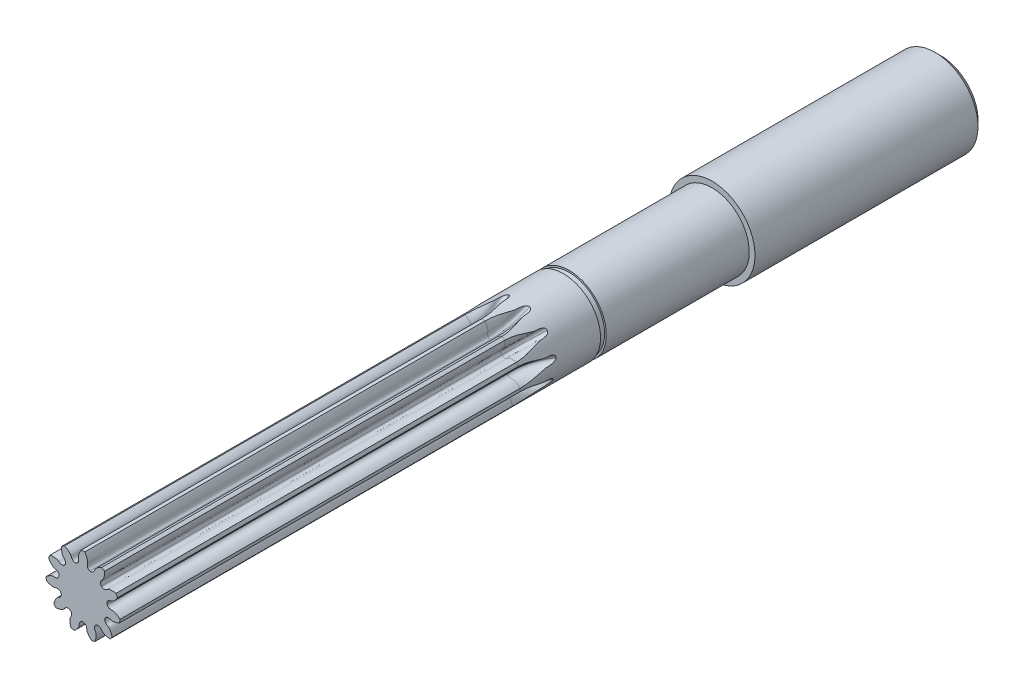
SolidWorks part; units mm, degrees
ref_plane "Спереди" through (0, 0, 0) normal (0, 0, 1) x (1, 0, 0)
ref_plane "Сверху" through (0, 0, 0) normal (0, 1, 0) x (1, 0, 0)
ref_plane "Справа" through (0, 0, 0) normal (1, 0, 0) x (0, 0, -1)
other "Configuration Table"
sketch "Эскиз1" plane through (0, 0, 0) normal (0, 0, 1) x (1, 0, 0)
  line L0 (0, 4.2505) -> (0, 6.5001) construction
  arc A6 (0.303, 6.493) -> (-0.303, 6.493) centre (0, 0) ccw
  arc A8 (3.7653, 5.2984) -> (3.2555, 5.6261) centre (0, 0) ccw
  arc A9 (6.0321, 2.4217) -> (5.7804, 2.9729) centre (0, 0) ccw
  arc A10 (6.3838, -1.224) -> (6.47, -0.6241) centre (0, 0) ccw
  arc A11 (4.7087, -4.481) -> (5.1055, -4.023) centre (0, 0) ccw
  arc A12 (1.5386, -6.3154) -> (2.12, -6.1446) centre (0, 0) ccw
  arc A13 (-2.12, -6.1446) -> (-1.5386, -6.3154) centre (0, 0) ccw
  arc A14 (-5.1055, -4.023) -> (-4.7087, -4.481) centre (0, 0) ccw
  arc A15 (-6.47, -0.6241) -> (-6.3838, -1.224) centre (0, 0) ccw
  arc A16 (-5.7804, 2.9729) -> (-6.0321, 2.4217) centre (0, 0) ccw
  arc A17 (-3.2555, 5.6261) -> (-3.7653, 5.2984) centre (0, 0) ccw
  arc A18 (-4.1999, 0.6538) -> (-4.214, 0.5559) centre (0, 0) ccw
  arc A19 (-3.1797, 2.8207) -> (-3.2445, 2.746) centre (0, 0) ccw
  arc A20 (-1.15, 4.092) -> (-1.2449, 4.0641) centre (0, 0) ccw
  arc A21 (1.2449, 4.0641) -> (1.15, 4.092) centre (0, 0) ccw
  arc A22 (3.2445, 2.746) -> (3.1797, 2.8207) centre (0, 0) ccw
  arc A23 (4.214, 0.5559) -> (4.1999, 0.6538) centre (0, 0) ccw
  arc A24 (3.8456, -1.8106) -> (3.8867, -1.7206) centre (0, 0) ccw
  arc A25 (2.2563, -3.6023) -> (2.3394, -3.5488) centre (0, 0) ccw
  arc A26 (-0.0494, -4.2502) -> (0.0494, -4.2502) centre (0, 0) ccw
  arc A27 (-2.3394, -3.5488) -> (-2.2563, -3.6023) centre (0, 0) ccw
  arc A28 (-3.8867, -1.7206) -> (-3.8456, -1.8106) centre (0, 0) ccw
  spline S0 degree 3 poles (0.303, 6.493) (0.3466, 6.4296) (0.4149, 6.3229) (0.5038, 6.1711) (0.5716, 6.0406) (0.6313, 5.9095) (0.6852, 5.7791) (0.7296, 5.6484) (0.7674, 5.5183) (0.798, 5.3728) (0.8278, 5.1961) (0.7682, 4.9723) (0.7367, 4.7556) (0.754, 4.5684) (0.7852, 4.4471) (0.829, 4.3517) (0.8776, 4.2755) (0.9328, 4.2146) (1.0177, 4.1438) (1.0937, 4.1064) (1.15, 4.092) knots 0 0 0 0 0.085617 0.14097 0.195721 0.24917 0.301247 0.352629 0.402768 0.451734 0.518548 0.599046 0.705842 0.760988 0.807057 0.844573 0.877292 0.907236 0.935686 1 1 1 1
  spline S1 degree 3 poles (-0.303, 6.493) (-0.3466, 6.4296) (-0.4149, 6.3229) (-0.5038, 6.1711) (-0.5716, 6.0406) (-0.6313, 5.9095) (-0.6852, 5.7791) (-0.7296, 5.6484) (-0.7674, 5.5183) (-0.798, 5.3728) (-0.8278, 5.1961) (-0.7682, 4.9723) (-0.7367, 4.7556) (-0.754, 4.5684) (-0.7852, 4.4471) (-0.829, 4.3517) (-0.8776, 4.2755) (-0.9328, 4.2146) (-1.0177, 4.1438) (-1.0937, 4.1064) (-1.15, 4.092) knots 0 0 0 0 0.085617 0.14097 0.195721 0.24917 0.301247 0.352629 0.402768 0.451734 0.518548 0.599046 0.705842 0.760988 0.807057 0.844573 0.877292 0.907236 0.935686 1 1 1 1
  spline S2 degree 3 poles (3.2555, 5.6261) (3.1845, 5.5963) (3.0694, 5.5435) (2.9125, 5.4638) (2.7849, 5.3907) (2.6639, 5.3126) (2.548, 5.2321) (2.4399, 5.1462) (2.3379, 5.0572) (2.2335, 4.9513) (2.1128, 4.8187) (2.042, 4.5983) (1.9513, 4.399) (1.8356, 4.2508) (1.7437, 4.1657) (1.6553, 4.1091) (1.5733, 4.0713) (1.4939, 4.0498) (1.3841, 4.0362) (1.3, 4.0458) (1.2449, 4.0641) knots 0 0 0 0 0.085617 0.14097 0.195721 0.24917 0.301247 0.352629 0.402768 0.451734 0.518548 0.599046 0.705842 0.760988 0.807057 0.844573 0.877292 0.907236 0.935686 1 1 1 1
  spline S3 degree 3 poles (3.7653, 5.2984) (3.7677, 5.2215) (3.7674, 5.0948) (3.7602, 4.9191) (3.7467, 4.7726) (3.7259, 4.6301) (3.7008, 4.4913) (3.6676, 4.3573) (3.629, 4.2274) (3.5761, 4.0885) (3.5056, 3.9237) (3.3345, 3.7676) (3.1908, 3.6024) (3.1041, 3.4356) (3.0649, 3.3166) (3.0502, 3.2127) (3.0498, 3.1224) (3.0633, 3.0412) (3.0965, 2.9357) (3.1402, 2.8632) (3.1797, 2.8207) knots 0 0 0 0 0.085617 0.14097 0.195721 0.24917 0.301247 0.352629 0.402768 0.451734 0.518548 0.599046 0.705842 0.760988 0.807057 0.844573 0.877292 0.907236 0.935686 1 1 1 1
  spline S4 degree 3 poles (5.7804, 2.9729) (5.7046, 2.9862) (5.5791, 3.004) (5.4041, 3.0219) (5.2573, 3.0293) (5.1132, 3.0291) (4.9722, 3.024) (4.8349, 3.0101) (4.7009, 2.9904) (4.5558, 2.9578) (4.3826, 2.9115) (4.2038, 2.7644) (4.0198, 2.6457) (3.8424, 2.5836) (3.719, 2.5617) (3.6141, 2.5619) (3.5246, 2.5744) (3.4462, 2.5993) (3.3465, 2.6472) (3.281, 2.7007) (3.2445, 2.746) knots 0 0 0 0 0.085617 0.14097 0.195721 0.24917 0.301247 0.352629 0.402768 0.451734 0.518548 0.599046 0.705842 0.760988 0.807057 0.844573 0.877292 0.907236 0.935686 1 1 1 1
  spline S5 degree 3 poles (6.0321, 2.4217) (5.9925, 2.3557) (5.9238, 2.2492) (5.8227, 2.1053) (5.7322, 1.9894) (5.6377, 1.8807) (5.5415, 1.7775) (5.4411, 1.6827) (5.3384, 1.5943) (5.2188, 1.5061) (5.0704, 1.4055) (4.8421, 1.3668) (4.6319, 1.3054) (4.4688, 1.212) (4.3714, 1.1331) (4.3029, 1.0537) (4.2537, 0.9778) (4.2212, 0.9023) (4.1921, 0.7956) (4.1897, 0.711) (4.1999, 0.6538) knots 0 0 0 0 0.085617 0.14097 0.195721 0.24917 0.301247 0.352629 0.402768 0.451734 0.518548 0.599046 0.705842 0.760988 0.807057 0.844573 0.877292 0.907236 0.935686 1 1 1 1
  spline S6 degree 3 poles (6.47, -0.6241) (6.4135, -0.572) (6.3176, -0.4892) (6.18, -0.3795) (6.0605, -0.2938) (5.9391, -0.2162) (5.8178, -0.1442) (5.6948, -0.0816) (5.5714, -0.0258) (5.4317, 0.0252) (5.261, 0.0799) (5.031, 0.0528) (4.812, 0.0524) (4.6292, 0.0961) (4.5136, 0.1444) (4.4254, 0.2013) (4.3569, 0.2602) (4.3044, 0.3235) (4.2465, 0.4177) (4.2203, 0.4982) (4.214, 0.5559) knots 0 0 0 0 0.085617 0.14097 0.195721 0.24917 0.301247 0.352629 0.402768 0.451734 0.518548 0.599046 0.705842 0.760988 0.807057 0.844573 0.877292 0.907236 0.935686 1 1 1 1
  spline S7 degree 3 poles (6.3838, -1.224) (6.3148, -1.2581) (6.1995, -1.3105) (6.0366, -1.3769) (5.8978, -1.4255) (5.7595, -1.4658) (5.6228, -1.5007) (5.4871, -1.5261) (5.3529, -1.5449) (5.2046, -1.5545) (5.0254, -1.5588) (4.8124, -1.468) (4.6023, -1.406) (4.4146, -1.3964) (4.2901, -1.4101) (4.1895, -1.4399) (4.1071, -1.4771) (4.0389, -1.5231) (3.9568, -1.5971) (3.909, -1.667) (3.8867, -1.7206) knots 0 0 0 0 0.085617 0.14097 0.195721 0.24917 0.301247 0.352629 0.402768 0.451734 0.518548 0.599046 0.705842 0.760988 0.807057 0.844573 0.877292 0.907236 0.935686 1 1 1 1
  spline S8 degree 3 poles (5.1055, -4.023) (5.0861, -3.9486) (5.0502, -3.827) (4.9937, -3.6604) (4.9395, -3.5237) (4.8795, -3.3928) (4.8163, -3.2667) (4.7466, -3.1475) (4.673, -3.0338) (4.5831, -2.9154) (4.469, -2.7771) (4.2609, -2.6756) (4.0765, -2.5575) (3.9463, -2.4219) (3.8751, -2.3188) (3.8317, -2.2233) (3.8059, -2.1366) (3.796, -2.055) (3.7981, -1.9445) (3.8196, -1.8626) (3.8456, -1.8106) knots 0 0 0 0 0.085617 0.14097 0.195721 0.24917 0.301247 0.352629 0.402768 0.451734 0.518548 0.599046 0.705842 0.760988 0.807057 0.844573 0.877292 0.907236 0.935686 1 1 1 1
  spline S9 degree 3 poles (4.7087, -4.481) (4.6322, -4.4724) (4.5068, -4.4542) (4.3339, -4.422) (4.1908, -4.3878) (4.0527, -4.3469) (3.9189, -4.3023) (3.791, -4.2503) (3.6679, -4.1937) (3.538, -4.1215) (3.3848, -4.0283) (3.2547, -3.8367) (3.1116, -3.671) (2.9588, -3.5615) (2.8467, -3.5057) (2.7459, -3.4763) (2.6565, -3.4631) (2.5743, -3.4649) (2.4652, -3.4828) (2.3872, -3.5157) (2.3394, -3.5488) knots 0 0 0 0 0.085617 0.14097 0.195721 0.24917 0.301247 0.352629 0.402768 0.451734 0.518548 0.599046 0.705842 0.760988 0.807057 0.844573 0.877292 0.907236 0.935686 1 1 1 1
  spline S10 degree 3 poles (2.12, -6.1446) (2.144, -6.0715) (2.1795, -5.9499) (2.222, -5.7792) (2.2503, -5.6349) (2.2706, -5.4922) (2.2856, -5.352) (2.2914, -5.214) (2.291, -5.0786) (2.2793, -4.9304) (2.2582, -4.7524) (2.138, -4.5545) (2.0467, -4.3554) (2.0105, -4.1709) (2.0063, -4.0457) (2.0215, -3.9419) (2.0466, -3.8551) (2.0824, -3.7811) (2.144, -3.6892) (2.2063, -3.6319) (2.2563, -3.6023) knots 0 0 0 0 0.085617 0.14097 0.195721 0.24917 0.301247 0.352629 0.402768 0.451734 0.518548 0.599046 0.705842 0.760988 0.807057 0.844573 0.877292 0.907236 0.935686 1 1 1 1
  spline S11 degree 3 poles (1.5386, -6.3154) (1.4789, -6.2668) (1.3833, -6.1836) (1.2552, -6.0631) (1.1533, -5.957) (1.0592, -5.8479) (0.9707, -5.738) (0.8913, -5.6252) (0.8184, -5.511) (0.7481, -5.38) (0.6696, -5.2188) (0.6638, -4.9873) (0.6329, -4.7705) (0.5636, -4.5958) (0.4995, -4.4882) (0.4306, -4.409) (0.3625, -4.3496) (0.2924, -4.3067) (0.1909, -4.2627) (0.1075, -4.2482) (0.0494, -4.2502) knots 0 0 0 0 0.085617 0.14097 0.195721 0.24917 0.301247 0.352629 0.402768 0.451734 0.518548 0.599046 0.705842 0.760988 0.807057 0.844573 0.877292 0.907236 0.935686 1 1 1 1
  spline S12 degree 3 poles (-1.5386, -6.3154) (-1.4789, -6.2668) (-1.3833, -6.1836) (-1.2552, -6.0631) (-1.1533, -5.957) (-1.0592, -5.8479) (-0.9707, -5.738) (-0.8913, -5.6252) (-0.8184, -5.511) (-0.7481, -5.38) (-0.6696, -5.2188) (-0.6638, -4.9873) (-0.6329, -4.7705) (-0.5636, -4.5958) (-0.4995, -4.4882) (-0.4306, -4.409) (-0.3625, -4.3496) (-0.2924, -4.3067) (-0.1909, -4.2627) (-0.1075, -4.2482) (-0.0494, -4.2502) knots 0 0 0 0 0.085617 0.14097 0.195721 0.24917 0.301247 0.352629 0.402768 0.451734 0.518548 0.599046 0.705842 0.760988 0.807057 0.844573 0.877292 0.907236 0.935686 1 1 1 1
  spline S13 degree 3 poles (-2.12, -6.1446) (-2.144, -6.0715) (-2.1795, -5.9499) (-2.222, -5.7792) (-2.2503, -5.6349) (-2.2706, -5.4922) (-2.2856, -5.352) (-2.2914, -5.214) (-2.291, -5.0786) (-2.2793, -4.9304) (-2.2582, -4.7524) (-2.138, -4.5545) (-2.0467, -4.3554) (-2.0105, -4.1709) (-2.0063, -4.0457) (-2.0215, -3.9419) (-2.0466, -3.8551) (-2.0824, -3.7811) (-2.144, -3.6892) (-2.2063, -3.6319) (-2.2563, -3.6023) knots 0 0 0 0 0.085617 0.14097 0.195721 0.24917 0.301247 0.352629 0.402768 0.451734 0.518548 0.599046 0.705842 0.760988 0.807057 0.844573 0.877292 0.907236 0.935686 1 1 1 1
  spline S14 degree 3 poles (-4.7087, -4.481) (-4.6322, -4.4724) (-4.5068, -4.4542) (-4.3339, -4.422) (-4.1908, -4.3878) (-4.0527, -4.3469) (-3.9189, -4.3023) (-3.791, -4.2503) (-3.6679, -4.1937) (-3.538, -4.1215) (-3.3848, -4.0283) (-3.2547, -3.8367) (-3.1116, -3.671) (-2.9588, -3.5615) (-2.8467, -3.5057) (-2.7459, -3.4763) (-2.6565, -3.4631) (-2.5743, -3.4649) (-2.4652, -3.4828) (-2.3872, -3.5157) (-2.3394, -3.5488) knots 0 0 0 0 0.085617 0.14097 0.195721 0.24917 0.301247 0.352629 0.402768 0.451734 0.518548 0.599046 0.705842 0.760988 0.807057 0.844573 0.877292 0.907236 0.935686 1 1 1 1
  spline S15 degree 3 poles (-5.1055, -4.023) (-5.0861, -3.9486) (-5.0502, -3.827) (-4.9937, -3.6604) (-4.9395, -3.5237) (-4.8795, -3.3928) (-4.8163, -3.2667) (-4.7466, -3.1475) (-4.673, -3.0338) (-4.5831, -2.9154) (-4.469, -2.7771) (-4.2609, -2.6756) (-4.0765, -2.5575) (-3.9463, -2.4219) (-3.8751, -2.3188) (-3.8317, -2.2233) (-3.8059, -2.1366) (-3.796, -2.055) (-3.7981, -1.9445) (-3.8196, -1.8626) (-3.8456, -1.8106) knots 0 0 0 0 0.085617 0.14097 0.195721 0.24917 0.301247 0.352629 0.402768 0.451734 0.518548 0.599046 0.705842 0.760988 0.807057 0.844573 0.877292 0.907236 0.935686 1 1 1 1
  spline S16 degree 3 poles (-6.3838, -1.224) (-6.3148, -1.2581) (-6.1995, -1.3105) (-6.0366, -1.3769) (-5.8978, -1.4255) (-5.7595, -1.4658) (-5.6228, -1.5007) (-5.4871, -1.5261) (-5.3529, -1.5449) (-5.2046, -1.5545) (-5.0254, -1.5588) (-4.8124, -1.468) (-4.6023, -1.406) (-4.4146, -1.3964) (-4.2901, -1.4101) (-4.1895, -1.4399) (-4.1071, -1.4771) (-4.0389, -1.5231) (-3.9568, -1.5971) (-3.909, -1.667) (-3.8867, -1.7206) knots 0 0 0 0 0.085617 0.14097 0.195721 0.24917 0.301247 0.352629 0.402768 0.451734 0.518548 0.599046 0.705842 0.760988 0.807057 0.844573 0.877292 0.907236 0.935686 1 1 1 1
  spline S17 degree 3 poles (-6.47, -0.6241) (-6.4135, -0.572) (-6.3176, -0.4892) (-6.18, -0.3795) (-6.0605, -0.2938) (-5.9391, -0.2162) (-5.8178, -0.1442) (-5.6948, -0.0816) (-5.5714, -0.0258) (-5.4317, 0.0252) (-5.261, 0.0799) (-5.031, 0.0528) (-4.812, 0.0524) (-4.6292, 0.0961) (-4.5136, 0.1444) (-4.4254, 0.2013) (-4.3569, 0.2602) (-4.3044, 0.3235) (-4.2465, 0.4177) (-4.2203, 0.4982) (-4.214, 0.5559) knots 0 0 0 0 0.085617 0.14097 0.195721 0.24917 0.301247 0.352629 0.402768 0.451734 0.518548 0.599046 0.705842 0.760988 0.807057 0.844573 0.877292 0.907236 0.935686 1 1 1 1
  spline S18 degree 3 poles (-6.0321, 2.4217) (-5.9925, 2.3557) (-5.9238, 2.2492) (-5.8227, 2.1053) (-5.7322, 1.9894) (-5.6377, 1.8807) (-5.5415, 1.7775) (-5.4411, 1.6827) (-5.3384, 1.5943) (-5.2188, 1.5061) (-5.0704, 1.4055) (-4.8421, 1.3668) (-4.6319, 1.3054) (-4.4688, 1.212) (-4.3714, 1.1331) (-4.3029, 1.0537) (-4.2537, 0.9778) (-4.2212, 0.9023) (-4.1921, 0.7956) (-4.1897, 0.711) (-4.1999, 0.6538) knots 0 0 0 0 0.085617 0.14097 0.195721 0.24917 0.301247 0.352629 0.402768 0.451734 0.518548 0.599046 0.705842 0.760988 0.807057 0.844573 0.877292 0.907236 0.935686 1 1 1 1
  spline S19 degree 3 poles (-5.7804, 2.9729) (-5.7046, 2.9862) (-5.5791, 3.004) (-5.4041, 3.0219) (-5.2573, 3.0293) (-5.1132, 3.0291) (-4.9722, 3.024) (-4.8349, 3.0101) (-4.7009, 2.9904) (-4.5558, 2.9578) (-4.3826, 2.9115) (-4.2038, 2.7644) (-4.0198, 2.6457) (-3.8424, 2.5836) (-3.719, 2.5617) (-3.6141, 2.5619) (-3.5246, 2.5744) (-3.4462, 2.5993) (-3.3465, 2.6472) (-3.281, 2.7007) (-3.2445, 2.746) knots 0 0 0 0 0.085617 0.14097 0.195721 0.24917 0.301247 0.352629 0.402768 0.451734 0.518548 0.599046 0.705842 0.760988 0.807057 0.844573 0.877292 0.907236 0.935686 1 1 1 1
  spline S20 degree 3 poles (-3.7653, 5.2984) (-3.7677, 5.2215) (-3.7674, 5.0948) (-3.7602, 4.9191) (-3.7467, 4.7726) (-3.7259, 4.6301) (-3.7008, 4.4913) (-3.6676, 4.3573) (-3.629, 4.2274) (-3.5761, 4.0885) (-3.5056, 3.9237) (-3.3345, 3.7676) (-3.1908, 3.6024) (-3.1041, 3.4356) (-3.0649, 3.3166) (-3.0502, 3.2127) (-3.0498, 3.1224) (-3.0633, 3.0412) (-3.0965, 2.9357) (-3.1402, 2.8632) (-3.1797, 2.8207) knots 0 0 0 0 0.085617 0.14097 0.195721 0.24917 0.301247 0.352629 0.402768 0.451734 0.518548 0.599046 0.705842 0.760988 0.807057 0.844573 0.877292 0.907236 0.935686 1 1 1 1
  spline S21 degree 3 poles (-3.2555, 5.6261) (-3.1845, 5.5963) (-3.0694, 5.5435) (-2.9125, 5.4638) (-2.7849, 5.3907) (-2.6639, 5.3126) (-2.548, 5.2321) (-2.4399, 5.1462) (-2.3379, 5.0572) (-2.2335, 4.9513) (-2.1128, 4.8187) (-2.042, 4.5983) (-1.9513, 4.399) (-1.8356, 4.2508) (-1.7437, 4.1657) (-1.6553, 4.1091) (-1.5733, 4.0713) (-1.4939, 4.0498) (-1.3841, 4.0362) (-1.3, 4.0458) (-1.2449, 4.0641) knots 0 0 0 0 0.085617 0.14097 0.195721 0.24917 0.301247 0.352629 0.402768 0.451734 0.518548 0.599046 0.705842 0.760988 0.807057 0.844573 0.877292 0.907236 0.935686 1 1 1 1
  point P469 (0, 0)
  point P490 (0, 0)
  dimension "D1" = 11
  dimension "D2" = 11
extrude "Бобышка-Вытянуть1" add sketch "Эскиз1" along normal blind 70
sketch "Эскиз3" plane through (0, 0, 0) normal (1, 0, 0) x (0, 0, -1)
  line L1 (0, 50) -> (0, -50) construction
  line L2 (40, 6.5) -> (40, 7.5)
  line L3 (40, 7.5) -> (79, 7.5)
  line L4 (80, 6.5) -> (80, 0)
  line L5 (80, 0) -> (0, 0)
  line L6 (0, 0) -> (0, 6.5)
  line L7 (0, 6.5) -> (14, 6.5)
  line L8 (14, 6.5) -> (14, 6.2)
  line L9 (14, 6.2) -> (15, 6.2)
  line L10 (15, 6.2) -> (15, 6.5)
  line L11 (15, 6.5) -> (40, 6.5)
  line L12 (79, 7.5) -> (80, 6.5)
  point P6 (80, 7.5)
  dimension "D1" = 80
  dimension "D2" = 25
  dimension "D3" = 40
  dimension "D4" = 7.5
  dimension "D5" = 1
  dimension "D6" = 0.3
  dimension "D7" = 6.5
  dimension "D8" = 6.5
revolve "Повернуть1" add sketch "Эскиз3" angle 360 about L5
sketch "Эскиз5" plane through (0, 0, 0) normal (0, 0, 1) x (1, 0, 0)
  line L9 (2.4864, 13.9291) -> (6.4361, 12.7693) construction
  arc A1 (4.6682, 5.8701) -> (-0.7535, 7.4621) centre (0, 0) ccw
  arc A2 (-0.7535, 7.4621) -> (0.303, 6.493) centre (3.1196, 10.6242) ccw
  arc A3 (3.2555, 5.6261) -> (4.6682, 5.8701) centre (3.1196, 10.6242) ccw
  arc A4 (1.15, 4.092) -> (1.2449, 4.0641) centre (0, 0) cw
  arc A6 (1.2449, 4.0641) -> (1.15, 4.092) centre (0, 0) ccw construction
  spline S0 degree 3 poles (1.15, 4.092) (1.0937, 4.1064) (1.0177, 4.1438) (0.9328, 4.2146) (0.8776, 4.2755) (0.829, 4.3517) (0.7852, 4.4471) (0.754, 4.5684) (0.7367, 4.7556) (0.7682, 4.9723) (0.8278, 5.1961) (0.798, 5.3728) (0.7674, 5.5183) (0.7296, 5.6484) (0.6852, 5.7791) (0.6313, 5.9095) (0.5716, 6.0406) (0.5038, 6.1711) (0.4149, 6.3229) (0.3466, 6.4296) (0.303, 6.493) knots 0 0 0 0 0.064314 0.092764 0.122708 0.155427 0.192943 0.239012 0.294158 0.400954 0.481452 0.548266 0.597232 0.647371 0.698753 0.75083 0.804279 0.85903 0.914383 1 1 1 1
  spline S1 degree 3 poles (1.2449, 4.0641) (1.3, 4.0458) (1.3841, 4.0362) (1.4939, 4.0498) (1.5733, 4.0713) (1.6553, 4.1091) (1.7437, 4.1657) (1.8356, 4.2508) (1.9513, 4.399) (2.042, 4.5983) (2.1128, 4.8187) (2.2335, 4.9513) (2.3379, 5.0572) (2.4399, 5.1462) (2.548, 5.2321) (2.6639, 5.3126) (2.7849, 5.3907) (2.9125, 5.4638) (3.0694, 5.5435) (3.1845, 5.5963) (3.2555, 5.6261) knots 0 0 0 0 0.064314 0.092764 0.122708 0.155427 0.192943 0.239012 0.294158 0.400954 0.481452 0.548266 0.597232 0.647371 0.698753 0.75083 0.804279 0.85903 0.914383 1 1 1 1
  dimension "D1" = 10.6242
  dimension "D2" = 15
revolve "Вырез-Повернуть1" cut sketch "Эскиз5" angle 360 about L9
pattern_circular "Круговой массив1" count 11 over 360 about axis through (0, 0, -80) along (0, 0, -1) of "Вырез-Повернуть1" reverse direction yes
